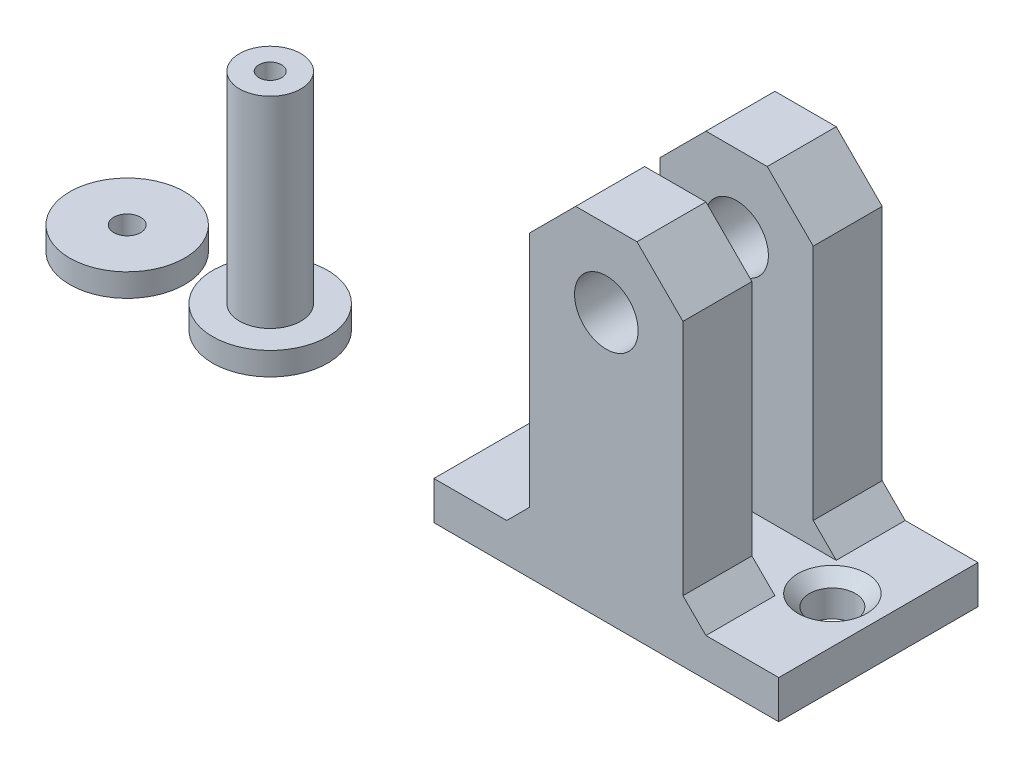
SolidWorks part; units mm, degrees
ref_plane "Front Plane" through (0, 0, 0) normal (0, 0, 1) x (1, 0, 0)
ref_plane "Top Plane" through (0, 0, 0) normal (0, 1, 0) x (1, 0, 0)
ref_plane "Right Plane" through (0, 0, 0) normal (1, 0, 0) x (0, 0, -1)
sketch "Sketch1" plane through (0, 0, 0) normal (0, 1, 0) x (1, 0, 0)
  line L0 (0, 13) -> (45, 13) construction
  line L1 (0, 0) -> (45, 0)
  line L2 (0, 0) -> (0, 26)
  line L3 (0, 26) -> (45, 26)
  line L4 (45, 0) -> (45, 26)
  line L5 (11.5, 16.5) -> (33.5, 16.5) construction
  line L6 (11.5, 16.5) -> (11.5, 9.5) construction
  line L7 (11.5, 9.5) -> (33.5, 9.5) construction
  line L8 (33.5, 16.5) -> (33.5, 9.5) construction
  line L9 (0, 0) -> (45, 0)
  line L10 (0, 0) -> (0, 9)
  line L11 (0, 9) -> (45, 9)
  line L12 (45, 0) -> (45, 9)
  line L13 (0, 17) -> (45, 17)
  line L14 (22.5, 26) -> (22.5, 0) construction
  line L15 (0, 26) -> (0, 17) construction
  line L16 (0, 0) -> (0, 9) construction
  line L17 (22.5, 26) -> (22.5, 17) construction
  line L18 (26.0796, 4.5) -> (24.2898, 1.4)
  line L19 (20.7102, 18.4) -> (24.2898, 18.4)
  line L20 (24.2898, 18.4) -> (26.0796, 21.5)
  line L21 (26.0796, 21.5) -> (24.2898, 24.6)
  line L22 (24.2898, 24.6) -> (20.7102, 24.6)
  line L23 (20.7102, 24.6) -> (18.9204, 21.5)
  line L24 (18.9204, 21.5) -> (20.7102, 18.4)
  line L25 (24.2898, 7.6) -> (26.0796, 4.5)
  line L26 (20.7102, 7.6) -> (24.2898, 7.6)
  line L27 (18.9204, 4.5) -> (20.7102, 7.6)
  line L28 (20.7102, 1.4) -> (18.9204, 4.5)
  line L29 (24.2898, 1.4) -> (20.7102, 1.4)
  circle A0 centre (6, 13) radius 3
  circle A1 centre (39, 13) radius 3
  circle A2 centre (22.5, 21.5) radius 3.1 construction
  circle A3 centre (22.5, 21.5) radius 1.75
  circle A4 centre (22.5, 4.5) radius 1.75
  point P9 (0, 13)
  point P10 (11.5, 13)
  point P11 (22.5, 9.5)
  point P12 (22.5, 0)
  dimension "D4" = 6.2
  dimension "D6" = 3.5
  dimension "D8" = 6
  dimension "D9" = 6
  dimension "D1" = 45
  dimension "D2" = 7
  dimension "D3" = 22
  dimension "D5" = 8
  dimension "D7" = 9
extrude "Boss-Extrude1" add sketch "Sketch1" along normal blind 5 contours L2 L13 L4 L3 L24 L23 L22 L21 L20 L19 | L13 L2 L11 L4 A0 A1 | L11 L2 L1 L4 L18 L29 L28 L27 L26 L25 | L23 L24 L19 L20 L21 L22 A3 | A4 | L29 L18 L25 L26 L27 L28 A4 | A3 region at (0.4589, 0, -4.5) region at (22.5, 0, -13) region at (0.4589, 0, -21.5) region at (25.1027, 0, -2.9974) region at (19.8973, 0, -19.9974) region at (22.5, 0, -21.5) region at (22.5, 0, -4.5)
extrude "Boss-Extrude2" add sketch "Sketch1<3>" along normal blind 45 contours L2 L13 L4 L3 L24 L23 L22 L21 L20 L19 | L11 L2 L1 L4 L18 L29 L28 L27 L26 L25 | L23 L24 L19 L20 L21 L22 A3 | L29 L18 L25 L26 L27 L28 A4 | A4 | A3 region at (0.4589, 0, -4.5) region at (0.4589, 0, -21.5) region at (25.1027, 0, -2.9974) region at (19.8973, 0, -19.9974) region at (22.5, 0, -21.5) region at (22.5, 0, -4.5)
sketch "Sketch1<3>" plane through (0, 0, 0) normal (0, 1, 0) x (1, 0, 0) same geometry as "Sketch1"
sketch "Sketch2" plane through (0, 0, 0) normal (0, 0, 1) x (1, 0, 0)
  line L0 (22.5, 0) -> (22.5, 35) construction
  line L1 (0, 0) -> (45, 0) construction
  line L3 (8, 43) -> (37, 43) construction
  line L4 (8, 43) -> (8, 5)
  line L5 (8, 5) -> (37, 5)
  line L6 (37, 43) -> (37, 5)
  line L7 (0, 45) -> (0, 0) construction
  circle A0 centre (22.5, 35) radius 11 construction
  circle A1 centre (22.5, 35) radius 4.15
  point P14 (22.5, 5)
  dimension "D1" = 22
  dimension "D3" = 8.3
  dimension "D2" = 35
  dimension "D4" = 5
  dimension "D5" = 8
  dimension "D6" = 8
extrude "Cut-Extrude1" cut sketch "Sketch2" against normal through all contours A1 region at (22.5, 35, 0)
sketch "Sketch3" plane through (0, 0, 0) normal (0, 0, 1) x (1, 0, 0)
  line L0 (0, 45) -> (45, 45) construction
  line L1 (12.5, 5) -> (32.5, 5)
  line L2 (12.5, 5) -> (12.5, 45)
  line L3 (12.5, 45) -> (32.5, 45)
  line L4 (32.5, 5) -> (32.5, 45)
  line L5 (12.5, 5) -> (32.5, 45) construction
  line L6 (12.5, 45) -> (32.5, 5) construction
  line L7 (45, 45) -> (45, 0) construction
  line L8 (0, 45) -> (45, 45)
  line L9 (0, 45) -> (0, 5)
  line L10 (0, 5) -> (45, 5)
  line L11 (45, 45) -> (45, 5)
  circle A0 centre (22.5, 35) radius 4.15
  circle A1 centre (22.5, 35) radius 4.15 construction
  point P5 (22.5, 25)
  line M4 (45, 0) -> (45, 45)
  line M5 (45, 45) -> (0, 45)
  line M6 (0, 45) -> (0, 0)
  dimension "D1" = 20
extrude "Cut-Extrude2" cut sketch "Sketch3" against normal through all contours L10 L2 M6 M5 | L4 L10 M4 M5 region at (6.25, 25, 0) region at (38.75, 25, 0)
chamfer "Chamfer1" distance 6 angle 45 4 edges at (12.5, 45, -4.5) (32.5, 45, -4.5) (32.5, 45, -21.5) (12.5, 45, -21.5)
chamfer "Chamfer2" distance 1.5 angle 45 2 edges at (6, 5, -10) (39, 5, -10)
chamfer "Chamfer3" distance 3 angle 45 4 edges at (32.5, 5, -4.5) (32.5, 5, -21.5) (12.5, 5, -4.5) (12.5, 5, -21.5)
sketch "Sketch4" plane through (0, 0, 0) normal (0, 1, 0) x (1, 0, 0)
  circle A0 centre (-35.4489, 14.0889) radius 1.475
  circle A1 centre (-35.4489, 14.0889) radius 4
  circle A2 centre (-35.4489, 14.0889) radius 7.5
  circle A3 centre (-53.6605, 13.6411) radius 7.5
  circle A4 centre (-53.6605, 13.6411) radius 1.75
  point P7 (0, 0)
  dimension "D1" = 8
  dimension "D2" = 2.95
  dimension "D3" = 15
  dimension "D4" = 15
  dimension "D5" = 3.5
extrude "Boss-Extrude3" add sketch "Sketch4" along normal blind 26.25 separate body contours A1 A0 region at (-39.3358, 0, -14.0889)
extrude "Boss-Extrude4" add sketch "Sketch4<3>" against normal blind 3 contours A2 A1 | A1 A0 | A3 A4 region at (-39.3358, 0, -14.0889) region at (-42.7368, 0, -14.0889) region at (-60.9483, 0, -13.6411)
sketch "Sketch4<3>" plane through (0, 0, 0) normal (0, 1, 0) x (1, 0, 0) same geometry as "Sketch4"
